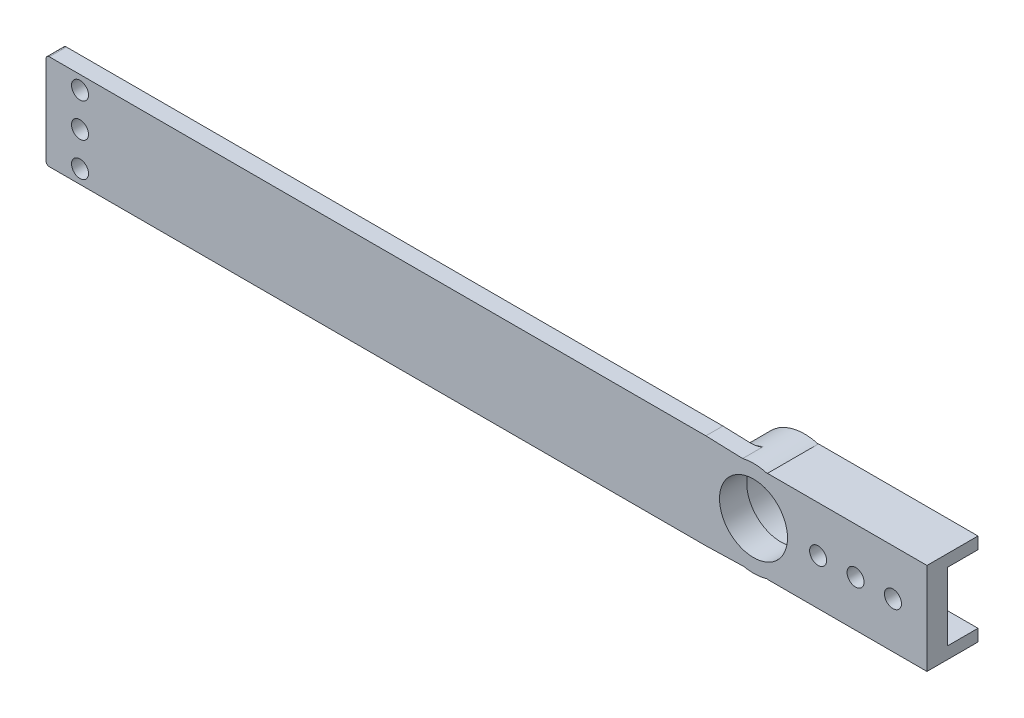
SolidWorks part; units mm, degrees
ref_plane "前视基准面" through (0, 0, 0) normal (0, 0, 1) x (1, 0, 0)
ref_plane "上视基准面" through (0, 0, 0) normal (0, 1, 0) x (1, 0, 0)
ref_plane "右视基准面" through (0, 0, 0) normal (1, 0, 0) x (0, 0, -1)
sketch "草图1" plane through (0, 0, 0) normal (0, 0, 1) x (1, 0, 0)
  line L1 (20, -10) -> (-20, -10)
  line L2 (20, -10) -> (20, 10)
  line L3 (20, 10) -> (-20, 10)
  line L4 (-20, -10) -> (-20, 10)
  line L5 (20, -10) -> (-20, 10) construction
  line L6 (20, 10) -> (-20, -10) construction
  point P0 (0, 0)
  dimension "D1" = 40
  dimension "D2" = 20
extrude "凸台-拉伸1" add sketch "草图1" along normal blind 6
sketch "草图2" plane through (0, 0, 6) normal (0, 0, 1) x (1, 0, 0)
  line L0 (20, -10) -> (20, 10) construction
  circle A0 centre (10, 0) radius 2.5
  circle A1 centre (-1, 0) radius 2.5
  circle A2 centre (-12, 0) radius 2.5
  dimension "D1" = 10
  dimension "D2" = 5
  dimension "D3" = 3
extrude "切除-拉伸1" cut sketch "草图2" against normal through all
sketch "草图3" plane through (0, 0, 6) normal (0, 0, 1) x (1, 0, 0)
  line L0 (20, 13.5) -> (20, 10)
  line L1 (20, -13.5) -> (-26.894, -13.5)
  line L3 (20, 13.5) -> (-26.894, 13.5)
  line L4 (-20, 10) -> (-20, -10)
  line L5 (-20, -10) -> (20, -10)
  line L6 (20, -10) -> (20, 10)
  line L7 (20, 10) -> (-20, 10)
  line L8 (-20, 10) -> (-20, -10)
  line L9 (-20, -10) -> (20, -10)
  line L10 (20, -10) -> (20, 10)
  line L11 (20, 10) -> (-20, 10)
  line L12 (-26.894, -13.5) -> (-26.894, 13.5)
  line L13 (20, -10.0394) -> (-26.894, 13.5) construction
  line L14 (20, 10.0394) -> (-26.894, -13.5) construction
  line L15 (20, -10) -> (20, -13.5)
  circle A0 centre (-31, 0) radius 11
  circle A1 centre (-31, 0) radius 14
  point P2 (0, 0)
  line M10 (-20, 10) -> (-20, -10)
  line M11 (-20, -10) -> (20, -10)
  line M13 (20, 10) -> (-20, 10)
  dimension "D3" = 22
  dimension "D4" = 28
  dimension "D2" = 3.5
  dimension "D1" = 0
extrude "凸台-拉伸2" add sketch "草图3" against normal blind 15 contours L3 A1 L1 L12 A0 | A1 L1 L15 M11 M10 | L1 A1 L8 A0 L12 | L8 A1 L3 L12 A0 | L8 A1 | A1 L0 L3 M10 M13 region at (-1.9449, 11.7771, 6) region at (-1.9449, -11.7771, 6) region at (-23.0173, 9.0328, 6) region at (-27.2274, 11.7946, 6) region at (-18.7882, 0, 6) region at (-23.0173, -9.0328, 6)
sketch "草图5" plane through (0, 0, 6) normal (0, 0, 1) x (1, 0, 0)
  circle A0 centre (-31, 0) radius 10
  circle A1 centre (-31, 0) radius 11 construction
  circle A2 centre (-31, 0) radius 11
  dimension "D1" = 20
extrude "凸台-拉伸3" add sketch "草图5" against normal blind 8
sketch "草图6" plane through (0, 0, 6) normal (0, 0, 1) x (1, 0, 0)
  circle A0 centre (-31, 0) radius 8.5
  circle A1 centre (-31, 0) radius 10 construction
  circle A2 centre (-31, 0) radius 10
  dimension "D1" = 17
sketch "草图8" plane through (0, 0, 6) normal (0, 0, 1) x (1, 0, 0)
  line L0 (20, -13.5) -> (20, 13.5) construction
  line L1 (20, -13.5) -> (-26.894, -13.5) construction
  line L2 (20, 13.5) -> (-26.894, 13.5) construction
  line L3 (20, -13.5) -> (20, 13.5)
  line L4 (20, -13.5) -> (-26.894, -13.5)
  line L5 (20, 13.5) -> (-26.894, 13.5)
  line L6 (-45, -14) -> (-26.894, -13.5)
  line L7 (-45, -14) -> (-239, -14)
  line L8 (-45, -14) -> (-45, 14)
  line L9 (-45, 14) -> (-239, 14)
  line L10 (-239, -14) -> (-239, 14)
  line L11 (-45, -14) -> (-239, 14) construction
  line L12 (-45, 14) -> (-239, -14) construction
  line L13 (-45, 14) -> (-26.894, 13.3843)
  line L14 (-12, 0) -> (-31, 0)
  arc A0 (-26.894, 13.3843) -> (-26.894, -13.3843) centre (-31, 0) ccw construction
  arc A1 (-26.894, 13.3843) -> (-26.894, -13.3843) centre (-31, 0) ccw
  point P6 (-142, 0)
  arc M11 (-26.894, 13.3843) -> (-26.894, -13.3843) centre (-31, 0) ccw
  dimension "D1" = 28
  dimension "D2" = 194
  dimension "D3" = 14
extrude "凸台-拉伸4" add sketch "草图8" against normal blind 5 contours L10 L7 L8 L9 | L8 L6 M11 | L13 L8 M11 region at (-42.1177, -10.7223, 6) region at (-142, 0, 6) region at (-42.1603, 10.6928, 6)
fillet "圆角1" radius 1 1 edges at (-44.9993, -0.1411, 1)
fillet "圆角2" radius 1 2 edges at (-239, 14, 3.5) (-239, -14, 3.5)
sketch "草图9" plane through (0, 0, 6) normal (0, 0, 1) x (1, 0, 0)
  line L0 (-239, 0) -> (-229, 0) construction
  line L1 (-239, -13) -> (-239, 13) construction
  circle A0 centre (-229, 0) radius 2.5
  circle A1 centre (-229, 10) radius 2.5
  circle A2 centre (-229, -10) radius 2.5
  dimension "D2" = 2
  dimension "5" = 5
  dimension "D1" = 10
  dimension "D3" = 2
extrude "切除-拉伸2" cut sketch "草图9" against normal blind 5
